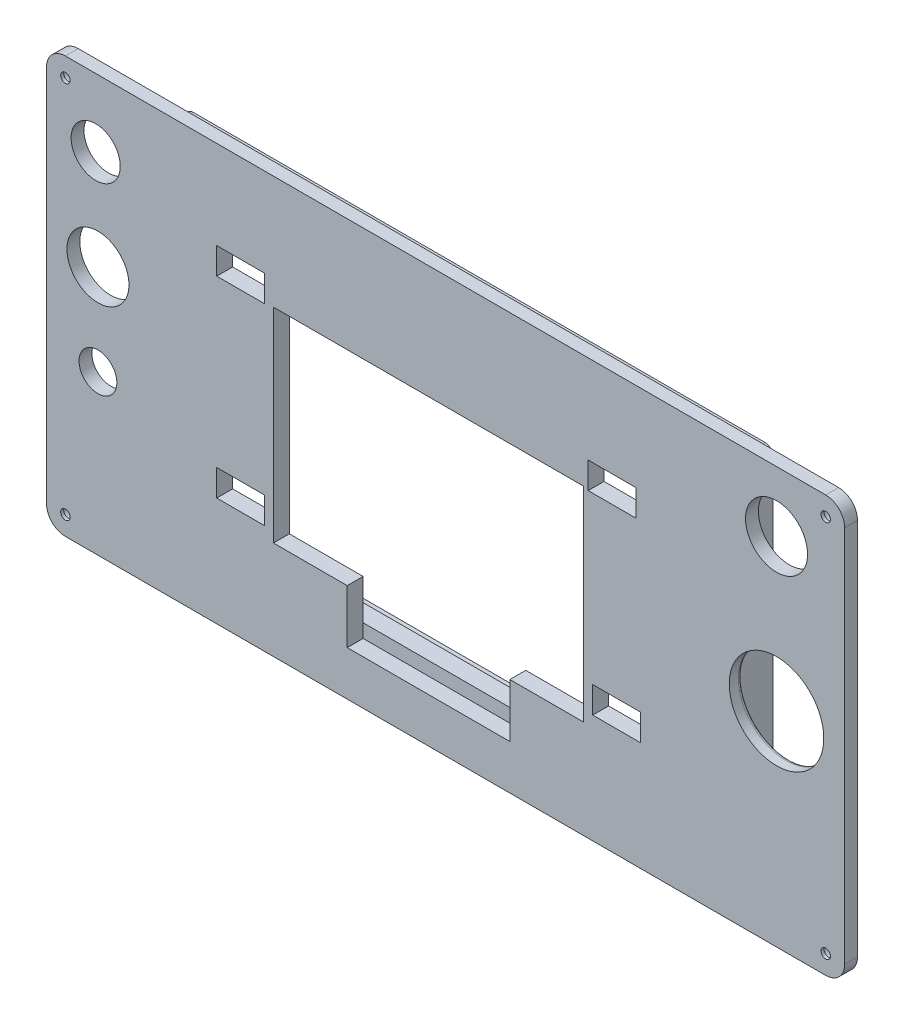
SolidWorks part; units mm, degrees
ref_plane "Front Plane" through (0, 0, 0) normal (0, 0, 1) x (1, 0, 0)
ref_plane "Top Plane" through (0, 0, 0) normal (0, 1, 0) x (1, 0, 0)
ref_plane "Right Plane" through (0, 0, 0) normal (1, 0, 0) x (0, 0, -1)
sketch "Sketch1" plane through (0, 0, 0) normal (0, 0, 1) x (1, 0, 0)
  line L1 (6.35, 0) -> (261.62, 0)
  line L2 (0, 6.35) -> (0, 133.35)
  line L3 (6.35, 139.7) -> (261.62, 139.7)
  line L4 (267.97, 6.35) -> (267.97, 133.35)
  arc A0 (6.35, 0) -> (0, 6.35) centre (6.35, 6.35) cw
  arc A1 (261.62, 0) -> (267.97, 6.35) centre (261.62, 6.35) ccw
  arc A2 (261.62, 139.7) -> (267.97, 133.35) centre (261.62, 133.35) cw
  arc A3 (0, 133.35) -> (6.35, 139.7) centre (6.35, 133.35) cw
  point P7 (0, 0)
  point P10 (267.97, 0)
  point P15 (0, 139.7)
  dimension "D3" = 6.35
  dimension "D1" = 139.7
  dimension "D2" = 267.97
extrude "Boss-Extrude1" add sketch "Sketch1" along normal blind 4.318
sketch "Sketch2" plane through (0, 0, 0) normal (0, 0, -1) x (-1, 0, 0)
  line L0 (-267.97, 6.35) -> (-267.97, 133.35) construction
  line L1 (-222.25, 125.73) -> (-34.29, 125.73)
  line L2 (-224.79, 123.19) -> (-224.79, 17.526)
  line L3 (-222.25, 14.986) -> (-34.29, 14.986)
  line L4 (-31.75, 123.19) -> (-31.75, 17.526)
  line L6 (-261.62, 139.7) -> (-6.35, 139.7) construction
  line L7 (-224.282, 127.762) -> (-32.258, 127.762)
  line L8 (-226.822, 125.222) -> (-226.822, 15.494)
  line L9 (-224.282, 12.954) -> (-32.258, 12.954)
  line L10 (-29.718, 125.222) -> (-29.718, 15.494)
  arc A0 (-224.79, 17.526) -> (-222.25, 14.986) centre (-222.25, 17.526) ccw
  arc A1 (-226.822, 15.494) -> (-224.282, 12.954) centre (-224.282, 15.494) ccw
  arc A2 (-32.258, 12.954) -> (-29.718, 15.494) centre (-32.258, 15.494) ccw
  arc A3 (-34.29, 14.986) -> (-31.75, 17.526) centre (-34.29, 17.526) ccw
  arc A4 (-32.258, 127.762) -> (-29.718, 125.222) centre (-32.258, 125.222) cw
  arc A5 (-34.29, 125.73) -> (-31.75, 123.19) centre (-34.29, 123.19) cw
  arc A6 (-224.282, 127.762) -> (-226.822, 125.222) centre (-224.282, 125.222) ccw
  arc A7 (-222.25, 125.73) -> (-224.79, 123.19) centre (-222.25, 123.19) ccw
  point P14 (-224.79, 14.986)
  point P25 (-31.75, 125.73)
  point P30 (-224.79, 125.73)
  dimension "D9" = 2.54
  dimension "D1" = 193.04
  dimension "D2" = 43.18
  dimension "D3" = 13.97
  dimension "D4" = 110.744
  dimension "D5" = 2.032
  dimension "D6" = 2.032
  dimension "D7" = 2.032
  dimension "D8" = 2.032
sketch "Sketch11" plane through (0, 0, 0) normal (0, 0, -1) x (-1, 0, 0)
  line L1 (-6.35, 0) -> (-261.62, 0) construction
  line L2 (-267.97, 6.35) -> (-267.97, 133.35) construction
  circle A0 centre (-245.11, 68.58) radius 15.875
  dimension "D1" = 31.75
  dimension "D2" = 22.86
  dimension "D3" = 68.58
extrude "Cut-Extrude4" cut sketch "Sketch11" against normal blind 5.08
sketch "Sketch12" plane through (0, 0, 0) normal (0, 0, -1) x (-1, 0, 0)
  line L0 (-267.97, 6.35) -> (-267.97, 133.35) construction
  line L1 (-261.62, 139.7) -> (-6.35, 139.7) construction
  line L4 (0, 133.35) -> (0, 6.35) construction
  circle A0 centre (-245.11, 119.38) radius 10.414
  circle A2 centre (-17.272, 83.82) radius 10.414
  circle A3 centre (-16.51, 116.84) radius 8.255
  circle A4 centre (-17.272, 53.34) radius 6.35
  dimension "D1" = 20.828
  dimension "D2" = 22.86
  dimension "D3" = 20.32
  dimension "D4" = 22.86
  dimension "D5" = 17.272
  dimension "D6" = 12.7
  dimension "D7" = 20.828
  dimension "D9" = 30.48
  dimension "D10" = 16.51
  dimension "D11" = 16.51
  dimension "D8" = 33.02
extrude "Cut-Extrude5" cut sketch "Sketch12" against normal blind 12.7
extrude "Boss-Extrude2" add sketch "Sketch2" along normal blind 12.7 separate body
sketch "Sketch15" plane through (0, 0, 0) normal (0, 0, -1) x (-1, 0, 0)
  line L0 (-255.27, 101.6) -> (-221.9744, 101.6) construction
  line L1 (-24.765, 102.87) -> (-8.255, 102.87) construction
  line L2 (-267.97, 6.35) -> (-267.97, 133.35) construction
  line L3 (-26.2101, 66.04) -> (-9.2587, 66.04) construction
  line L4 (-26.2101, 40.64) -> (-9.2587, 40.64) construction
  line L5 (-233.6331, 3.0623) -> (-21.8187, 3.0623) construction
  circle A0 centre (-245.11, 119.38) radius 10.414 construction
  circle A1 centre (-16.51, 116.84) radius 8.255 construction
  circle A2 centre (-17.272, 83.82) radius 10.414 construction
  circle A3 centre (-17.272, 53.34) radius 6.35 construction
  text T0 "ON / OFF"
  text T1 "  LASER"
  text T2 "   ARM"
  text T3 "    FIRE"
  text T4 "                                              EW GAME OF DRONES " font "Century Gothic" height in points 16
  dimension "D4" = 17.78
  dimension "D1" = 17.78
  dimension "D2" = 12.7
  dimension "D3" = 13.97
  dimension "D5" = 12.7
extrude "Cut-Extrude7" cut sketch "Sketch15" against normal blind 2.54
sketch "Sketch17" plane through (0, 0, 0) normal (0, 0, -1) x (-1, 0, 0)
  line L0 (-31.75, 17.526) -> (-31.75, 123.19) construction
  line L1 (-224.79, 127) -> (-31.75, 127)
  line L2 (-224.79, 127) -> (-224.79, 13.8903)
  line L3 (-224.79, 13.8903) -> (-31.75, 13.8903)
  line L4 (-31.75, 127) -> (-31.75, 13.8903)
extrude "Boss-Extrude3" add sketch "Sketch17" along normal blind 1.016
sketch "Sketch16" plane through (0, 0, 0) normal (0, 0, -1) x (-1, 0, 0)
  line L0 (-222.25, 14.986) -> (-34.29, 14.986) construction
  line L1 (-180.34, 101.6) -> (-76.2, 101.6)
  line L2 (-180.34, 101.6) -> (-180.34, 33.02)
  line L3 (-180.34, 33.02) -> (-155.575, 33.02)
  line L4 (-76.2, 101.6) -> (-76.2, 33.02)
  line L6 (-223.52, 127) -> (-223.52, 13.8903) construction
  line L7 (-30.48, 127) -> (-223.52, 127) construction
  line L8 (-155.575, 33.02) -> (-155.575, 14.986)
  line L9 (-155.575, 14.986) -> (-100.965, 14.986)
  line L10 (-100.965, 33.02) -> (-100.965, 14.986)
  line L13 (-100.965, 33.02) -> (-76.2, 33.02)
  point P8 (-128.27, 33.02)
  dimension "D1" = 43.18
  dimension "D2" = 104.14
  dimension "D3" = 25.4
  dimension "D4" = 68.58
  dimension "D5" = 54.61
extrude "Cut-Extrude8" cut sketch "Sketch16" against normal blind 5.08 and the other way through all
sketch "Sketch19" plane through (0, 0, 0) normal (0, 0, -1) x (-1, 0, 0)
  line L0 (-261.62, 139.7) -> (-6.35, 139.7) construction
  line L1 (-267.97, 6.35) -> (-267.97, 133.35) construction
  line L2 (0, 133.35) -> (0, 6.35) construction
  line L3 (-6.35, 0) -> (-261.62, 0) construction
  circle A0 centre (-261.62, 133.35) radius 1.5875
  circle A1 centre (-6.35, 133.35) radius 1.5875
  circle A2 centre (-261.62, 6.35) radius 1.5875
  circle A3 centre (-6.35, 6.35) radius 1.5875
  dimension "D1" = 3.175
  dimension "D2" = 3.175
  dimension "D3" = 3.175
  dimension "D4" = 3.175
  dimension "D5" = 6.35
  dimension "D6" = 6.35
  dimension "D7" = 6.35
  dimension "D8" = 6.35
  dimension "D9" = 6.35
  dimension "D10" = 6.35
  dimension "D11" = 6.35
  dimension "D12" = 6.35
extrude "Cut-Extrude10" cut sketch "Sketch19" against normal through all
sketch "Sketch20" plane through (0, 0, 0) normal (0, 0, -1) x (-1, 0, 0)
  circle A0 centre (-261.62, 133.35) radius 2.794
  circle A1 centre (-261.62, 6.35) radius 2.794
  circle A2 centre (-6.35, 133.35) radius 2.794
  circle A3 centre (-6.35, 6.35) radius 2.794
  dimension "D1" = 5.588
  dimension "D2" = 5.588
  dimension "D3" = 5.588
  dimension "D4" = 5.588
extrude "Cut-Extrude11" cut sketch "Sketch20" against normal blind 3.302
fillet "Fillet1" radius 1.27 1 edges at (229.235, 68.58, 0)
sketch "Sketch21" plane through (0, 125.73, 0) normal (0, -1, 0) x (-1, 0, 0)
  line L1 (-224.79, 1.016) -> (-212.09, 1.016)
  line L2 (-224.79, 1.016) -> (-224.79, 6.858)
  line L3 (-224.79, 6.858) -> (-212.09, 6.858)
  line L4 (-212.09, 1.016) -> (-212.09, 6.858)
  line L5 (-31.75, 1.016) -> (-44.45, 1.016)
  line L6 (-31.75, 1.016) -> (-31.75, 6.858)
  line L7 (-31.75, 6.858) -> (-44.45, 6.858)
  line L8 (-44.45, 1.016) -> (-44.45, 6.858)
  dimension "D1" = 5.842
  dimension "D2" = 5.842
  dimension "D3" = 12.7
  dimension "D4" = 12.7
  dimension "D5" = 167.64
extrude "Boss-Extrude5" add sketch "Sketch21" along normal blind 112.014
sketch "Sketch22" plane through (224.79, 0, 0) normal (-1, 0, 0) x (0, 0, 1)
  line L1 (-1.016, 127) -> (-6.858, 127)
  line L2 (-1.016, 127) -> (-1.016, 121.158)
  line L3 (-1.016, 121.158) -> (-6.858, 121.158)
  line L4 (-6.858, 127) -> (-6.858, 121.158)
  line L5 (-1.016, 13.97) -> (-6.858, 13.97)
  line L6 (-1.016, 13.97) -> (-1.016, 19.558)
  line L7 (-1.016, 19.558) -> (-6.858, 19.558)
  line L8 (-6.858, 13.97) -> (-6.858, 19.558)
  dimension "D1" = 5.842
  dimension "D2" = 5.842
  dimension "D3" = 5.842
  dimension "D4" = 5.588
  dimension "D5" = 101.6
extrude "Boss-Extrude6" add sketch "Sketch22" along normal blind 193.04
sketch "Sketch18" plane through (0, 0, -1.016) normal (0, 0, -1) x (-1, 0, 0)
  line L0 (-212.09, 19.558) -> (-212.09, 121.158) construction
  line L1 (-197.866, 109.982) -> (-181.864, 109.982)
  line L2 (-197.866, 109.982) -> (-197.866, 101.092)
  line L3 (-197.866, 101.092) -> (-181.864, 101.092)
  line L4 (-181.864, 109.982) -> (-181.864, 101.092)
  line L5 (-73.152, 109.982) -> (-57.15, 109.982)
  line L6 (-73.152, 109.982) -> (-73.152, 101.092)
  line L7 (-73.152, 101.092) -> (-57.15, 101.092)
  line L8 (-57.15, 109.982) -> (-57.15, 101.092)
  line L9 (-73.152, 45.466) -> (-57.15, 45.466)
  line L10 (-73.152, 45.466) -> (-73.152, 36.576)
  line L11 (-73.152, 36.576) -> (-57.15, 36.576)
  line L12 (-57.15, 45.466) -> (-57.15, 36.576)
  line L13 (-199.39, 45.466) -> (-183.388, 45.466)
  line L14 (-199.39, 45.466) -> (-199.39, 36.576)
  line L15 (-199.39, 36.576) -> (-183.388, 36.576)
  line L16 (-183.388, 45.466) -> (-183.388, 36.576)
  line L21 (-44.45, 19.558) -> (-44.45, 121.158) construction
  line L22 (-44.45, 121.158) -> (-212.09, 121.158) construction
  line L23 (-44.45, 19.558) -> (-212.09, 19.558) construction
  point P16 (-57.15, 105.537)
  dimension "D1" = 16.002
  dimension "D2" = 8.89
  dimension "D3" = 16.002
  dimension "D4" = 8.89
  dimension "D5" = 16.002
  dimension "D6" = 8.89
  dimension "D7" = 16.002
  dimension "D8" = 8.89
  dimension "D9" = 14.224
  dimension "D10" = 12.7
  dimension "D11" = 12.7
  dimension "D12" = 12.7
  dimension "D13" = 11.176
  dimension "D14" = 17.018
  dimension "D15" = 17.018
  dimension "D16" = 11.176
extrude "Cut-Extrude9" cut sketch "Sketch18" against normal blind 11.43
sketch "Sketch23" plane through (267.97, 0, 0) normal (1, 0, 0) x (0, 0, -1)
  line L1 (-8.6133, 141.3529) -> (0, 141.3529)
  line L2 (-8.6133, 141.3529) -> (-8.6133, -3.5712)
  line L3 (-8.6133, -3.5712) -> (0, -3.5712)
  line L4 (0, 141.3529) -> (0, -3.5712)
extrude "Cut-Extrude12" [suppressed] cut sketch "Sketch23" against normal blind 406.4
sketch "Sketch24" plane through (226.822, 0, 0) normal (1, 0, 0) x (0, 0, -1)
  line L0 (12.7, 125.222) -> (12.7, 15.494) construction
  circle A0 centre (12.7, 29.6922) radius 6.985
  dimension "D1" = 13.97
extrude "Cut-Extrude13" cut sketch "Sketch24" against normal blind 2.54
